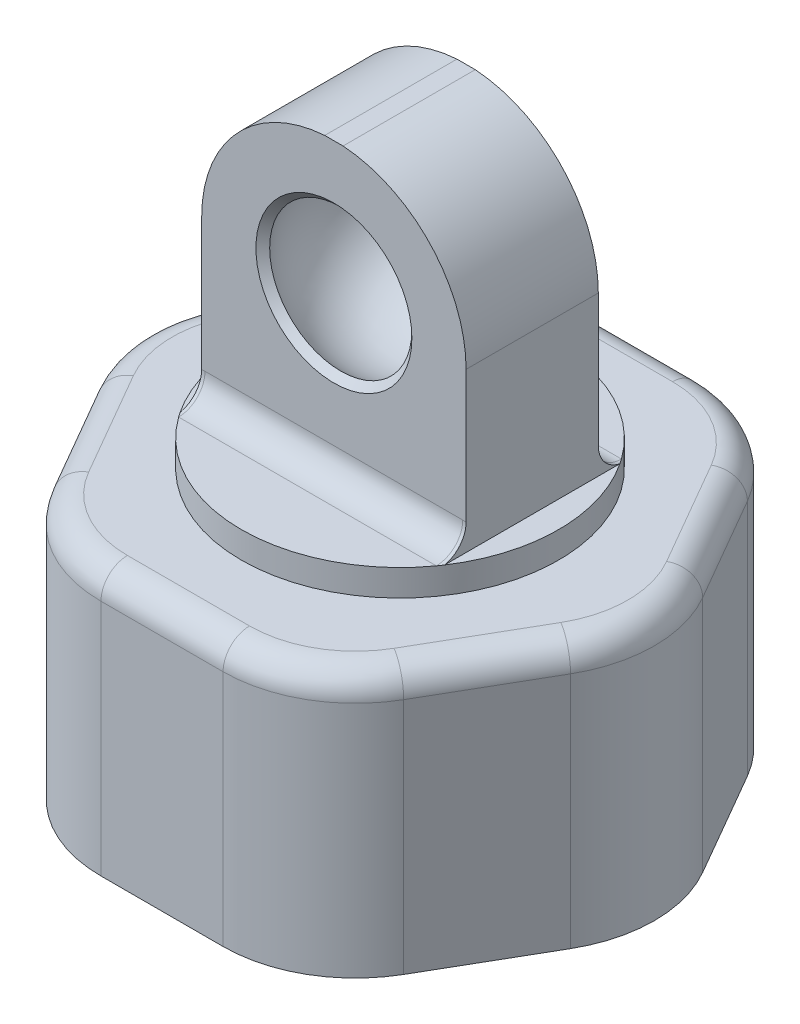
SolidWorks part; units mm, degrees
material "1060 Alloy"
ref_plane "Front Plane" through (0, 0, 0) normal (0, 0, 1) x (1, 0, 0)
ref_plane "Top Plane" through (0, 0, 0) normal (0, 1, 0) x (1, 0, 0)
ref_plane "Right Plane" through (0, 0, 0) normal (1, 0, 0) x (0, 0, -1)
sketch "Sketch1" plane through (0, 0, 0) normal (0, 1, 0) x (1, 0, 0)
  line L1 (10.3923, 0) -> (5.1962, 9)
  line L2 (5.1962, 9) -> (-5.1962, 9)
  line L3 (-5.1962, 9) -> (-10.3923, 0)
  line L4 (-10.3923, 0) -> (-5.1962, -9)
  line L5 (-5.1962, -9) -> (5.1962, -9)
  line L6 (5.1962, -9) -> (10.3923, 0)
  circle A0 centre (0, 0) radius 9 construction
  dimension "D1" = 18
extrude "Boss-Extrude1" add sketch "Sketch1" along normal blind 10
fillet "Fillet1" radius 5 6 edges at (-10.3923, 5, 0) (-5.1962, 5, -9) (5.1962, 5, -9) (10.3923, 5, 0) (-5.1962, 5, 9) (5.1962, 5, 9)
fillet "Fillet2" radius 1 12 edges at (-4.8094, 10, -8.3301) (0, 10, -9) (4.8094, 10, -8.3301) (7.7942, 10, -4.5) (9.6188, 10, 0) (7.7942, 10, 4.5) (4.8094, 10, 8.3301) (0, 10, 9) (-4.8094, 10, 8.3301) (-7.7942, 10, 4.5) (-9.6188, 10, 0) (-7.7942, 10, -4.5)
sketch "Sketch2" plane through (0, 10, 0) normal (0, 1, 0) x (1, 0, 0)
  circle A0 centre (0, 0) radius 6
  dimension "D1" = 12
extrude "Cut-Extrude1" cut sketch "Sketch2" against normal blind 2
sketch "Sketch3" plane through (0, 8, 0) normal (0, 1, 0) x (1, 0, 0)
  circle A0 centre (0, 0) radius 6
extrude "Boss-Extrude2" add sketch "Sketch3" along normal blind 3 separate body
sketch "Sketch4" plane through (0, 0, 0) normal (0, 0, 1) x (1, 0, 0)
  line L0 (0, 5) -> (0, 17) construction
  line L1 (6, 11) -> (-6, 11) construction
  line L2 (-5, 5) -> (-5, 17)
  line L3 (5, 5) -> (5, 17)
  arc A0 (-5, 5) -> (5, 5) centre (0, 5) ccw
  arc A1 (5, 17) -> (-5, 17) centre (0, 17) ccw
  point P5 (0, 11)
  dimension "D1" = 10
  dimension "D2" = 6
extrude "Boss-Extrude3" add sketch "Sketch4" along normal mid plane 5
sketch "Sketch5" plane through (0, 0, 0) normal (0, 0, 1) x (1, 0, 0)
  line L0 (-4.5, 17) -> (-3.5, 17)
  line L1 (3.5, 17) -> (4.5, 17)
  line L2 (0, 17) -> (3.5, 17) construction
  line L3 (-3.5, 17) -> (3.5, 17)
  arc A0 (3.5, 17) -> (-3.5, 17) centre (0, 17) ccw
  arc A1 (4.5, 17) -> (-4.5, 17) centre (0, 17) ccw
  circle A2 centre (0, 17) radius 4.5 construction
  circle A3 centre (0, 17) radius 3.5 construction
  dimension "D1" = 7
  dimension "D2" = 1
revolve "Revolve1" add sketch "Sketch5" angle 360 about L2 region at (0, 21.3994, 0) region at (0, 18.4854, 0)
revolve "Cut-Revolve2" cut sketch "Sketch5<7>" angle 360 about L2 region at (0, 18.4854, 0)
sketch "Sketch5<7>" plane through (0, 0, 0) normal (0, 0, 1) x (1, 0, 0) same geometry as "Sketch5"
sketch "Sketch6" plane through (-5, 0, 0) normal (-1, 0, 0) x (0, 0, 1)
  line L0 (2.5, 17) -> (2.5, 22) construction
  line L1 (-2.5, 11) -> (2.5, 11)
  line L2 (-2.5, 11) -> (-2.5, 21.988)
  line L3 (-2.5, 21.988) -> (2.5, 21.988)
  line L4 (2.5, 11) -> (2.5, 21.988)
  line L6 (-5.3632, 22.1915) -> (6, 22.1915)
  line L7 (-5.3632, 22.1915) -> (-5.3632, 11)
  line L8 (-5.3632, 11) -> (6, 11)
  line L9 (6, 22.1915) -> (6, 11)
  line M1 (-2.5, 17) -> (-2.5, 11)
  line M3 (2.5, 11) -> (2.5, 17)
extrude "Cut-Extrude2" cut sketch "Sketch6" against normal blind 13 contours L9 L6 L7 L8 L2 L3 L4 M1 M3 region at (-5, 11.1595, -3.9316)
chamfer "Chamfer1" distance 0.5 angle 45 2 edges at (2.4495, 17, 2.5) (-2.4495, 17, -2.5) first distance on face at (0, 16.9683, 2.5) first distance on face at (0, 16.9683, -2.5)
fillet "Fillet3" radius 1 2 edges at (0, 11, 2.5) (0, 11, -2.5)
